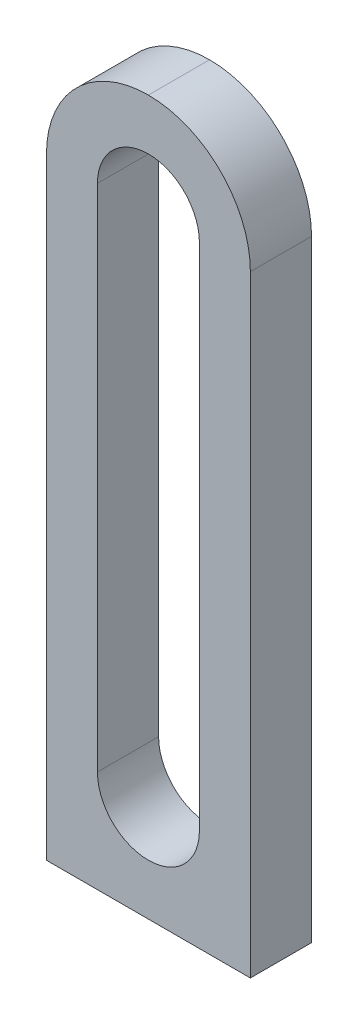
SolidWorks part; units mm, degrees
material "Wrought Stainless Steel"
ref_plane "Front Plane" through (0, 0, 0) normal (0, 0, 1) x (1, 0, 0)
ref_plane "Top Plane" through (0, 0, 0) normal (0, 1, 0) x (1, 0, 0)
ref_plane "Right Plane" through (0, 0, 0) normal (1, 0, 0) x (0, 0, -1)
sketch "Sketch1" plane through (0, 0, 0) normal (0, 0, 1) x (1, 0, 0)
  line L0 (0, -12.5) -> (0, 12.5) construction
  line L1 (-5, -17.5) -> (5, -17.5)
  line L2 (-5, -17.5) -> (-5, 17.5)
  line L3 (-5, 17.5) -> (5, 17.5)
  line L4 (5, -17.5) -> (5, 17.5)
  line L5 (-5, -17.5) -> (5, 17.5) construction
  line L6 (-5, 17.5) -> (5, -17.5) construction
  line L7 (-2.5, -12.5) -> (-2.5, 12.5)
  line L8 (2.5, -12.5) -> (2.5, 12.5)
  arc A0 (-2.5, -12.5) -> (2.5, -12.5) centre (0, -12.5) ccw
  arc A1 (2.5, 12.5) -> (-2.5, 12.5) centre (0, 12.5) ccw
  point P0 (0, 0)
  point P8 (0, 0)
  dimension "D3" = 2.5
  dimension "D1" = 35
  dimension "D2" = 10
  dimension "D4" = 25
base flange "Base-Flange1" sketch "Sketch1" thickness 3 reverse thickness direction no parameters "D1"=1
fillet "Fillet1" radius 5 2 edges at (-5, 17.5, -1.5) (5, 17.5, -1.5)
sketch "Bend-Lines1" [suppressed] plane through (0, 0, 0) normal (0, 1, 0) x (1, 0, 0)
sketch "Bounding-Box1" [suppressed] plane through (0, 0, 0) normal (0, 1, 0) x (1, 0, 0)
sheet metal parameters "Sheet-Metal1" thickness 3 parameters "D1"=1
flat pattern "Flat-Pattern1" [suppressed]
sketch "Bend-Lines2" plane through (0, 0, 0) normal (0, 1, 0) x (1, 0, 0)
sketch3d "Bounding-Box2" [suppressed]
  line L0 (5, 17.4998, 0) -> (5, -17.5, 0) construction
  line L1 (-5, 17.4998, 0) -> (-5, -17.5, 0) construction
  line L2 (5, 17.4998, 0) -> (-5, 17.4998, 0) construction
  line L3 (5, -17.5, 0) -> (-5, -17.5, 0) construction
